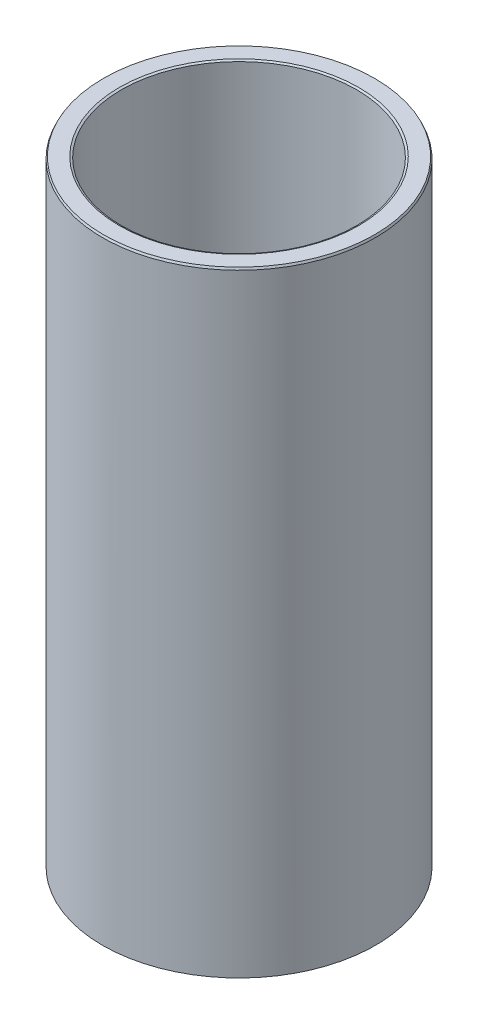
SolidWorks part; units mm, degrees
ref_plane "Front Plane" through (0, 0, 0) normal (0, 0, 1) x (1, 0, 0)
ref_plane "Top Plane" through (0, 0, 0) normal (0, 1, 0) x (1, 0, 0)
ref_plane "Right Plane" through (0, 0, 0) normal (1, 0, 0) x (0, 0, -1)
sketch "Sketch1" plane through (0, 0, 0) normal (0, 1, 0) x (1, 0, 0)
  circle A0 centre (0, 0) radius 45
  dimension "SLEEVE_OD" = 90
extrude "Boss-Extrude1" add sketch "Sketch1" along normal blind 203.058
sketch "Sketch2" plane through (0, 0, 0) normal (0, 1, 0) x (1, 0, 0)
  circle A0 centre (0, 0) radius 38.7991
  dimension "BORE_D" = 77.5983
extrude "Cut-Extrude1" cut sketch "Sketch2" along normal through all
chamfer "Chamfer1" distance 0.6625 angle 26.018 4 edges at (0, 203.058, 38.7991) (0, 0, 38.7991) (0, 0, 45) (0, 203.058, 45) first distance on face at (0, 203.058, 38.7991) first distance on face at (0, 0, 38.7991) first distance on face at (0, 203.058, 45)
